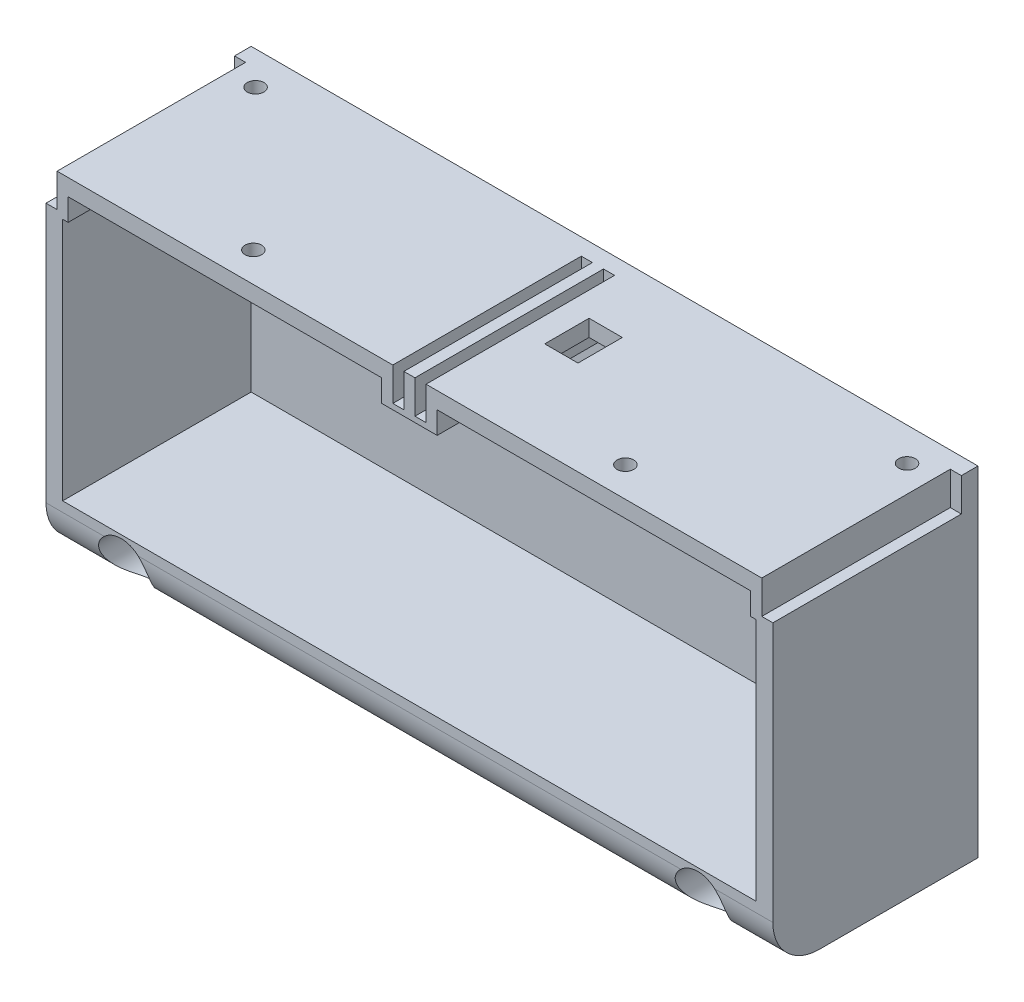
SolidWorks part; units mm, degrees
material "ABS"
ref_plane "Alzado" through (0, 0, 0) normal (0, 0, 1) x (1, 0, 0)
ref_plane "Planta" through (0, 0, 0) normal (0, 1, 0) x (1, 0, 0)
ref_plane "Vista lateral" through (0, 0, 0) normal (1, 0, 0) x (0, 0, -1)
sketch "Croquis2" plane through (0, 0, 0) normal (0, 0, 1) x (1, 0, 0)
  line L0 (0, 0) -> (131.1, 0)
  line L1 (131.1, 0) -> (131.1, -54)
  line L2 (131.1, -54) -> (0, -54)
  line L3 (0, -54) -> (0, 0)
  dimension "D1" = 131.1
  dimension "D2" = 54
extrude "Saliente-Extruir2" add sketch "Croquis2" along normal blind 3
sketch "Croquis3" plane through (0, 0, 3) normal (0, 0, 1) x (1, 0, 0)
  line L0 (0, -6) -> (2, -6)
  line L1 (0, 0) -> (0, -54) construction
  line L2 (2, -6) -> (2, 0)
  line L3 (131.1, 0) -> (0, 0) construction
  line L4 (2, 0) -> (129.1, 0)
  line L5 (129.1, 0) -> (129.1, -6)
  line L6 (129.1, -6) -> (131.1, -6)
  line L7 (131.1, -54) -> (131.1, 0) construction
  line L8 (131.1, -6) -> (131.1, -54)
  line L9 (131.1, -54) -> (0, -54)
  line L10 (0, -54) -> (0, -6)
  line L11 (65.55, 0) -> (66.55, 0)
  line L12 (65.55, 0) -> (64.55, 0)
  line L13 (64.55, 0) -> (64.55, -6)
  line L14 (66.55, 0) -> (66.55, -6)
  line L15 (64.55, -6) -> (62.55, -6)
  line L16 (62.55, -6) -> (62.55, 0)
  line L17 (66.55, -6) -> (68.55, -6)
  line L18 (68.55, -6) -> (68.55, 0)
  line L19 (3, -7) -> (128.1, -7)
  line L20 (128.1, -7) -> (128.1, -51)
  line L21 (128.1, -51) -> (3, -51)
  line L22 (3, -51) -> (3, -7)
  point P31 (130.1, -6)
  line M15 (0, 0) -> (0, -54)
  line M16 (0, -54) -> (131.1, -54)
  line M17 (131.1, -54) -> (131.1, 0)
  line M18 (131.1, 0) -> (0, 0)
  dimension "D1" = 2
  dimension "D2" = 2
  dimension "D3" = 6
  dimension "D4" = 2
  dimension "D5" = 2
  dimension "D6" = 1
  dimension "D7" = 1
  dimension "D8" = 3
  dimension "D9" = 3
  dimension "D10" = 3
  dimension "D11" = 1
extrude "Saliente-Extruir3" add sketch "Croquis3" along normal blind 34 contours L18 L17 L14 L4 L13 L15 L16 L2 L0 L6 L5 L21 L22 L19 L20 M18 M15 M16 M17 region at (1, -7.4179, 3)
sketch "Croquis4" plane through (0, -54, 0) normal (0, -1, 0) x (1, 0, 0)
  line L4 (0, 0) -> (131.1, 0)
  line L5 (131.1, 0) -> (131.1, 37)
  line L6 (131.1, 37) -> (0, 37)
  line L7 (0, 37) -> (0, 0)
  line L8 (0, 0) -> (131.1, 0)
  line L9 (131.1, 0) -> (131.1, 37)
  line L10 (131.1, 37) -> (0, 37)
  line L11 (0, 37) -> (0, 0)
  dimension "D1" = 0
extrude "Saliente-Extruir4" add sketch "Croquis4" along normal blind 7.2
sketch "Croquis5" plane through (0, 0, 37) normal (0, 0, 1) x (1, 0, 0)
  line L0 (3, -7) -> (128.1, -7) construction
  line L1 (4, -7) -> (60.55, -7)
  line L2 (4, -7) -> (4, -3)
  line L3 (4, -3) -> (60.55, -3)
  line L4 (60.55, -7) -> (60.55, -3)
  line L5 (62.55, 0) -> (2, 0) construction
  line L6 (65.55, -7) -> (65.55, 0) construction
  line L7 (66.55, 0) -> (64.55, 0) construction
  line L8 (127.1, -3) -> (70.55, -3)
  line L9 (70.55, -7) -> (70.55, -3)
  line L10 (127.1, -7) -> (70.55, -7)
  line L11 (127.1, -7) -> (127.1, -3)
  dimension "D1" = 1
  dimension "D2" = 2
  dimension "D3" = 3
extrude "Cortar-Extruir1" cut sketch "Croquis5" against normal up to vertex (34 mm away) up to point (3, -7, 3)
sketch "Croquis6" plane through (0, -3, 0) normal (0, -1, 0) x (1, 0, 0)
  line L0 (60.55, 37) -> (4, 37) construction
  line L1 (0, 37) -> (0, 3) construction
  line L2 (131.1, 37) -> (131.1, 3) construction
  line L3 (131.1, 0) -> (0, 0) construction
  line L4 (127.1, 3) -> (70.55, 3) construction
  line L5 (72.95, 20) -> (78.95, 20)
  line L6 (72.95, 20) -> (72.95, 12)
  line L7 (72.95, 12) -> (78.95, 12)
  line L8 (78.95, 20) -> (78.95, 12)
  circle A0 centre (32, 31.6) radius 1.5
  circle A1 centre (99.1, 31.6) radius 1.5
  circle A2 centre (6.8, 6) radius 1.5
  circle A3 centre (124.3, 6) radius 1.5
  point P16 (63.45, 31.6)
  dimension "D3" = 3
  dimension "D1" = 5.4
  dimension "D2" = 32
  dimension "D4" = 32
  dimension "D5" = 6.8
  dimension "D6" = 6
  dimension "D7" = 6.8
  dimension "D8" = 63.45
  dimension "D9" = 4.4
  dimension "D10" = 9
  dimension "D11" = 6
  dimension "D12" = 8
extrude "Cortar-Extruir2" cut sketch "Croquis6" against normal up to next
sketch "Croquis8" plane through (0, 0, 37) normal (0, 0, 1) x (1, 0, 0)
  line L0 (65.55, -61.2) -> (65.55, -51) construction
  line L1 (131.1, -61.2) -> (0, -61.2) construction
  line L2 (128.1, -51) -> (3, -51) construction
  circle A0 centre (13.55, -56.1) radius 4.5
  circle A1 centre (117.55, -56.1) radius 4.5
  point P8 (65.55, -56.1)
  dimension "D1" = 9
  dimension "D2" = 52
extrude "Cortar-Extruir3" cut sketch "Croquis8" against normal blind 33
sketch "Croquis9" plane through (0, 0, 37) normal (0, 0, 1) x (1, 0, 0)
  circle A0 centre (13.55, -56.1) radius 2.5
  circle A1 centre (117.55, -56.1) radius 2.5
  dimension "D1" = 5
extrude "Cortar-Extruir4" cut sketch "Croquis9" against normal through all
fillet "Redondeo1" radius 8.4 1 edges at (65.55, -61.2, 37)
